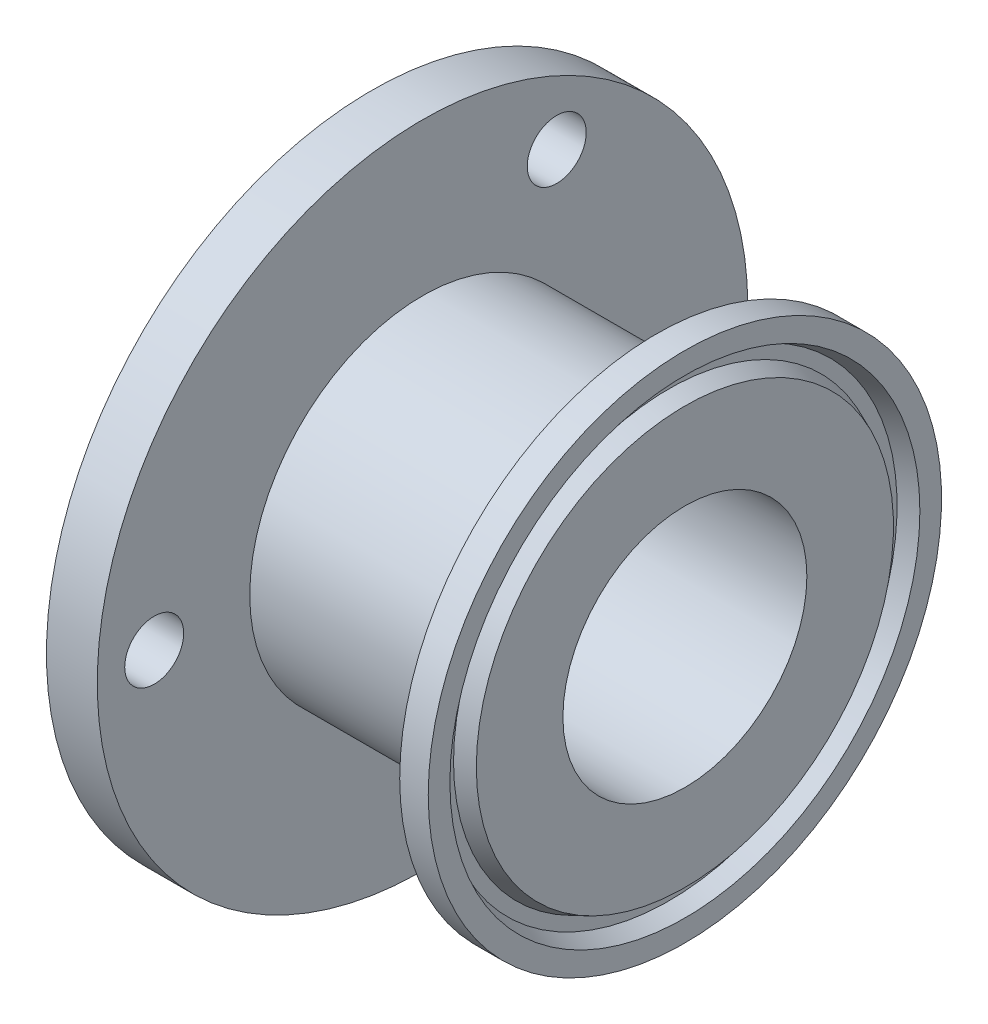
SolidWorks part; units mm, degrees
note: '?' marks a value the reader was unsure of.
material "6061 Alloy"
ref_plane "Front Plane" through (0, 0, 0) normal (0, 0, 1) x (1, 0, 0)
ref_plane "Top Plane" through (0, 0, 0) normal (0, 1, 0) x (1, 0, 0)
ref_plane "Right Plane" through (0, 0, 0) normal (1, 0, 0) x (0, 0, -1)
sketch "Sketch1" plane through (0, 0, 0) normal (0, 0, 1) x (1, 0, 0)
  line L0 (-15.4047, 12) -> (-15.4047, 34)
  line L1 (-15.4047, 34) -> (-10.4047, 34)
  line L2 (-10.4047, 34) -> (-10.4047, 17)
  line L3 (-10.4047, 17) -> (8.7949, 17)
  line L4 (9.869, 17.7521) -> (12.598, 25.25)
  line L5 (12.598, 25.25) -> (15.4047, 25.25)
  line L6 (15.4047, 25.25) -> (15.4047, 23.1186)
  line L7 (15.4047, 12) -> (-15.4047, 12)
  line L8 (0, 0) -> (52.6945, 0) construction
  line L9 (0, 12) -> (0, 0) construction
  line L10 (15.4047, 23.1186) -> (13.8299, 22.4501)
  line L11 (13.8299, 22.4501) -> (13.8299, 21.1871)
  line L12 (13.8299, 21.1871) -> (15.4047, 20.5186)
  line L13 (13.8299, 21.8186) -> (15.4047, 21.8186) construction
  line L14 (15.4047, 20.5186) -> (15.4047, 12)
  arc A0 (8.7949, 17) -> (9.869, 17.7521) centre (8.7949, 18.143) ccw
  circle A1 centre (15.4047, 21.8186) radius 1.15 construction
  point P16 (9.5953, 17)
  dimension "D9" = 1.143
  dimension "D14" = 2.3
  dimension "D1" = 20
  dimension "D2" = 25.25
  dimension "D3" = 2.8067
  dimension "D4" = 5
  dimension "D5" = 68
  dimension "D6" = 5
  dimension "D7" = 20
  dimension "D8" = 22
  dimension "D10" = 46
  dimension "D11" = 21.8186
  dimension "D12" = 1.5748
  dimension "D13" = 2.6
revolve "Revolve1" add sketch "Sketch1" angle 360 about L8
hole_wizard "M5 Clearance Hole1" positions "Sketch2" profile "Sketch4" hole size "M5" standard "ISO"
sketch "Sketch2" plane through (-15.4047, 0, 0) normal (-1, 0, 0) x (0, 0, 1)
  point P0 (-13.2, -22.8631)
  point P3 (-13.2, 22.8631)
  point P6 (26.4, 0)
sketch "Sketch4" plane through (-15.4047, -22.8631, -13.2) normal (0, 1, 0) x (0, 0, 1)
  line L0 (0, 0) -> (0, 6.7415)
  line L1 (0, 6.7415) -> (2.9, 4.999)
  line L2 (2.9, 4.999) -> (2.9, 0)
  line L5 (2.9, 0) -> (0, 0)
  line L10 (0, 6.7415) -> (-2.9, 4.999) construction
  line L11 (0, -6.35) -> (0, 107.95) construction
  dimension "Hole Dia." = 5.8
  dimension "Hole Depth" = 4.999
  dimension "Drill Angle" = 118
fillet "Fillet1" [suppressed] radius 1.1938
fillet "Fillet2" [suppressed] radius 0.7874
sketch "Sketch5" plane through (-10.4047, 0, 0) normal (1, 0, 0) x (0, 0, -1)
  circle A0 centre (0, 0) radius 32
  dimension "D1" = 64
extrude "Cut-Extrude-Thin1" cut sketch "Sketch5" against normal through all thin thin type one direction wall 10
ref_axis "Axis1" through (-12.5452, 0, 0) along (1, 0, 0)?
